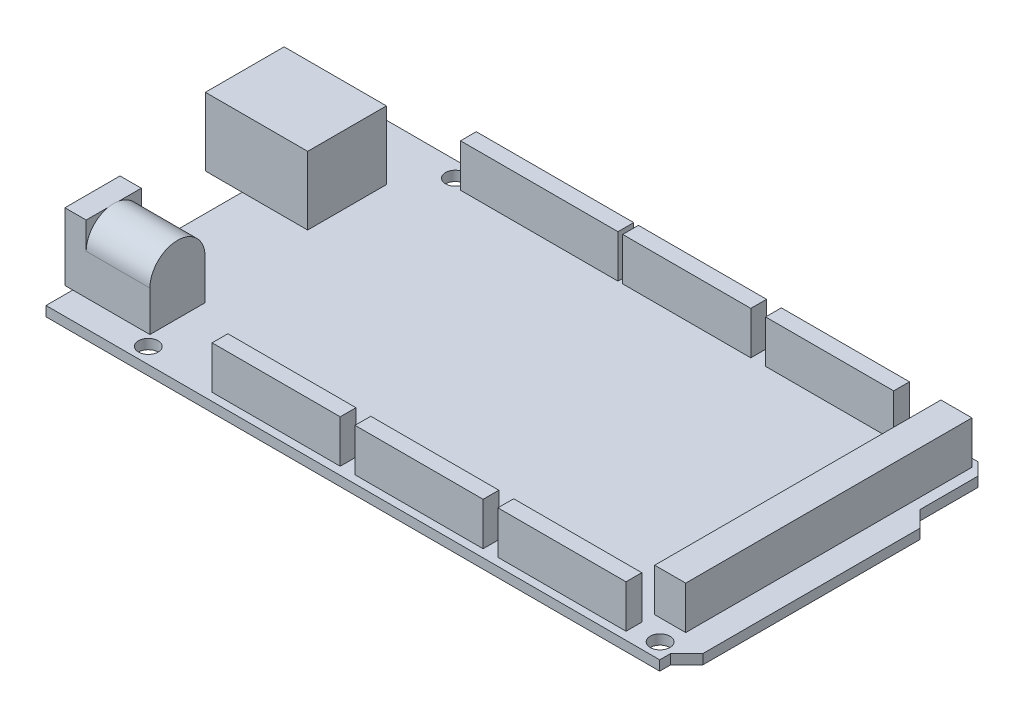
SolidWorks part; units mm, degrees
ref_plane "Front" through (0, 0, 0) normal (0, 0, 1) x (1, 0, 0)
ref_plane "Top" through (0, 0, 0) normal (0, 1, 0) x (1, 0, 0)
ref_plane "Right" through (0, 0, 0) normal (1, 0, 0) x (0, 0, -1)
sketch "Sketch1" plane through (0, 0, 0) normal (0, 1, 0) x (1, 0, 0)
  line L0 (0, 0) -> (0, 53.34)
  line L1 (0, 53.34) -> (97, 53.34)
  line L2 (97, 53.34) -> (99, 51.34)
  line L3 (99, 51.34) -> (99, 41.95)
  line L4 (99, 41.95) -> (101.6, 39.35)
  line L5 (101.6, 39.35) -> (101.6, 4.35)
  line L6 (101.6, 4.35) -> (99, 1.75)
  line L7 (99, 1.75) -> (99, 0)
  line L8 (99, 0) -> (0, 0)
  line L9 (46.1899, 3.81) -> (48.5775, 3.81) construction
  line L10 (17.3355, 52.07) -> (42.7355, 52.07)
  line L11 (17.3355, 52.07) -> (17.3355, 49.53)
  line L12 (17.3355, 49.53) -> (42.7355, 49.53)
  line L13 (42.7355, 52.07) -> (42.7355, 49.53)
  line L14 (43.4975, 52.07) -> (64.1604, 52.07)
  line L15 (43.4975, 52.07) -> (43.4975, 49.53)
  line L16 (43.4975, 49.53) -> (64.1604, 49.53)
  line L17 (64.1604, 52.07) -> (64.1604, 49.53)
  line L18 (66.548, 52.07) -> (87.2109, 52.07)
  line L19 (66.548, 52.07) -> (66.548, 49.53)
  line L20 (66.548, 49.53) -> (87.2109, 49.53)
  line L21 (87.2109, 52.07) -> (87.2109, 49.53)
  line L22 (97.2909, 52.07) -> (92.2909, 52.07)
  line L23 (97.2909, 52.07) -> (97.2909, 5.9)
  line L24 (97.2909, 5.9) -> (92.2909, 5.9)
  line L25 (92.2909, 52.07) -> (92.2909, 5.9)
  line L26 (92.2909, 3.81) -> (71.628, 3.81)
  line L27 (92.2909, 3.81) -> (92.2909, 1.27)
  line L28 (92.2909, 1.27) -> (71.628, 1.27)
  line L29 (71.628, 3.81) -> (71.628, 1.27)
  line L30 (69.2404, 1.27) -> (48.5775, 1.27)
  line L31 (69.2404, 1.27) -> (69.2404, 3.81)
  line L32 (69.2404, 3.81) -> (48.5775, 3.81)
  line L33 (48.5775, 1.27) -> (48.5775, 3.81)
  line L34 (46.1899, 1.27) -> (25.527, 1.27)
  line L35 (46.1899, 1.27) -> (46.1899, 3.81)
  line L36 (46.1899, 3.81) -> (25.527, 3.81)
  line L37 (25.527, 1.27) -> (25.527, 3.81)
  line L38 (69.2404, 3.81) -> (71.628, 3.81) construction
  line L39 (64.1604, 52.07) -> (66.548, 52.07) construction
  line L40 (2.16, 13.208) -> (2.16, 4.318)
  line L41 (-5.9309, 44.34) -> (10.5691, 44.34)
  line L42 (-5.9309, 44.34) -> (-5.9309, 31.64)
  line L43 (-5.9309, 31.64) -> (10.5691, 31.64)
  line L44 (10.5691, 44.34) -> (10.5691, 31.64)
  line L45 (-1.27, 13.208) -> (12.446, 13.208)
  line L46 (-1.27, 13.208) -> (-1.27, 4.318)
  line L47 (-1.27, 4.318) -> (12.446, 4.318)
  line L48 (12.446, 13.208) -> (12.446, 4.318)
  circle A0 centre (96.52, 2.54) radius 1.5875
  circle A1 centre (71.0748, 7.62) radius 1.5875
  circle A2 centre (13.97, 2.54) radius 1.5875
  circle A3 centre (15.24, 50.8) radius 1.5875
  circle A4 centre (90.17, 50.8) radius 1.5875
  point P48 (17.3355, 50.8)
  point P49 (25.527, 2.54)
  point P50 (16.8275, 50.8)
  dimension "D15" = 3.175
  dimension "D1" = 101.6
  dimension "D2" = 99
  dimension "D3" = 135
  dimension "D4" = 1.75
  dimension "D5" = 35
  dimension "D6" = 97
  dimension "D7" = 53.34
  dimension "D8" = 2.54
  dimension "D9" = 96.52
  dimension "D10" = 71.0748
  dimension "D11" = 7.62
  dimension "D12" = 90.17
  dimension "D13" = 15.24
  dimension "D14" = 50.8
  dimension "D16" = 13.97
  dimension "D17" = 25.4
  dimension "D18" = 20.6629
  dimension "D19" = 2.3876
  dimension "D20" = 2.54
  dimension "D21" = 0.762
  dimension "D22" = 5.08
  dimension "D23" = 0.508
  dimension "D24" = 5
  dimension "D25" = 46.17
  dimension "D26" = 9
  dimension "D27" = 16.5
  dimension "D28" = 12.7
  dimension "D29" = 5.9309
  dimension "D30" = 1.27
  dimension "D31" = 4.318
  dimension "D32" = 8.89
  dimension "D33" = 13.716
  dimension "D34" = 3.43
extrude "Boss-Extrude1" add sketch "Sketch1" along normal blind 1.5875 contours L45 L48 L47 L0 L8 L7 L6 L5 L4 L3 L2 L1 L41 L44 L43 A4 A3 A2 A1 A0 L29 L26 L27 L28 L25 L22 L23 L24 L10 L13 L12 L11 L14 L17 L16 L15 L18 L21 L20 | L44 L41 L0 L43 | L48 L45 L0 L47 | L17 L14 L15 L16 | L13 L10 L11 L12 | L21 L18 L19 L20 | L22 L25 L24 L23 | L26 L29 L28 L27 | L33 L30 L31 L32 | L37 L34 L35 L36 | L0 L47 L40 L45 region at (50.1465, 0, -26.5078) region at (1.08, 0, -8.763) region at (7.303, 0, -8.763) region at (5.2846, 0, -37.99) region at (30.0355, 0, -50.8) region at (53.8289, 0, -50.8) region at (76.8794, 0, -50.8) region at (94.7909, 0, -28.985) region at (81.9595, 0, -2.54) region at (58.909, 0, -2.54) region at (35.8585, 0, -2.54)
extrude "Boss-Extrude2" add sketch "Sketch1<3>" along normal blind 11 from surface contours L42 L43 L0 L41 | L44 L41 L0 L43 region at (-2.9654, 0, -37.99) region at (5.2846, 0, -37.99) starting at face at (90.17, 1.5875, -49.2125)
sketch "Sketch1<3>" plane through (0, 0, 0) normal (0, 1, 0) x (1, 0, 0) same geometry as "Sketch1"
extrude "Boss-Extrude3" add sketch "Sketch1<4>" along normal blind 6.5 from surface contours L48 L45 L40 L47 region at (7.303, 0, -8.763) starting at face at (90.17, 1.5875, -49.2125)
sketch "Sketch1<4>" plane through (0, 0, 0) normal (0, 1, 0) x (1, 0, 0) same geometry as "Sketch1"
extrude "Boss-Extrude4" add sketch "Sketch1<5>" along normal blind 10.86 from surface contours L46 L47 L0 L45 | L0 L47 L40 L45 region at (-0.635, 0, -8.763) region at (1.08, 0, -8.763) starting at face at (7.303, 1.5875, -8.763)
sketch "Sketch1<5>" plane through (0, 0, 0) normal (0, 1, 0) x (1, 0, 0) same geometry as "Sketch1"
sketch "Sketch2" plane through (0, 8.0875, 0) normal (0, 1, 0) x (1, 0, 0)
  line L0 (2.16, 8.763) -> (12.446, 8.763)
  line L1 (2.16, 4.318) -> (2.16, 13.208) construction
  line L2 (12.446, 4.318) -> (12.446, 13.208) construction
  line L3 (12.446, 8.763) -> (12.446, 4.318)
  line L4 (12.446, 4.318) -> (2.16, 4.318)
  line L5 (2.16, 4.318) -> (2.16, 8.763)
revolve "Revolve1" add sketch "Sketch2" angle 180 about L0 reverse direction yes
extrude "Boss-Extrude5" add sketch "Sketch1<6>" along normal blind 8.5 contours L33 L30 L31 L32 | L26 L29 L28 L27 | L22 L25 L24 L23 | L36 L37 L34 L35 | L18 L21 L20 L19 | L16 L17 L14 L15 | L12 L13 L10 L11 region at (94.7909, 0, -28.985) region at (81.9595, 0, -2.54) region at (58.909, 0, -2.54)
sketch "Sketch1<6>" plane through (0, 0, 0) normal (0, 1, 0) x (1, 0, 0) same geometry as "Sketch1"
